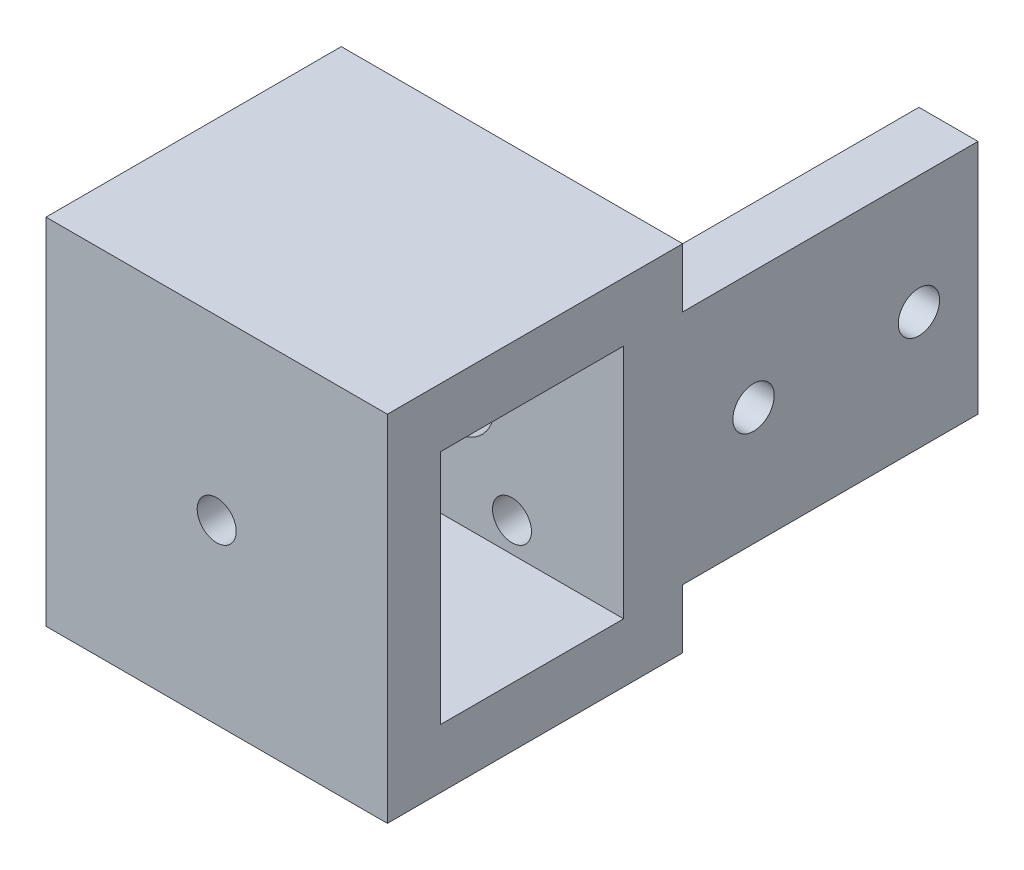
SolidWorks part; units mm, degrees
ref_plane "前视基准面" through (0, 0, 0) normal (0, 0, 1) x (1, 0, 0)
ref_plane "上视基准面" through (0, 0, 0) normal (0, 1, 0) x (1, 0, 0)
ref_plane "右视基准面" through (0, 0, 0) normal (1, 0, 0) x (0, 0, -1)
sketch "草图1" plane through (0, 0, 0) normal (0, 0, 1) x (1, 0, 0)
  line L0 (0, 10) -> (28.9, 10) construction
  line L1 (0, 20) -> (28.9, 20)
  line L2 (0, 20) -> (0, 0)
  line L3 (0, 0) -> (28.9, 0)
  line L4 (28.9, 20) -> (28.9, 0)
  line L6 (14.45, 20) -> (14.45, -18.7145) construction
  line L11 (0, 20) -> (28.9, 20)
  line L12 (0, 20) -> (0, 25)
  line L13 (0, 25) -> (28.9, 25)
  line L14 (28.9, 20) -> (28.9, 25)
  line L15 (0, 0) -> (28.9, 0)
  line L16 (0, 0) -> (0, -5)
  line L17 (0, -5) -> (28.9, -5)
  line L18 (28.9, 0) -> (28.9, -5)
  circle A0 centre (9.45, 17.5) radius 1.65
  circle A1 centre (19.45, 17.5) radius 1.65
  circle A2 centre (9.45, 2.5) radius 1.65
  circle A3 centre (19.45, 2.5) radius 1.65
  dimension "D3" = 3.3
  dimension "D5" = 2.5
  dimension "D1" = 20
  dimension "D2" = 28.9
  dimension "D4" = 9.45
  dimension "D6" = 5
  dimension "D7" = 5
extrude "凸台-拉伸1" add sketch "草图1" along normal blind 5 contours L4 L1 L2 L3 A3 A1 A0 A2 | L4 region at (14.45, 10, 0)
sketch "草图2" plane through (28.9, 0, 0) normal (1, 0, 0) x (0, 0, -1)
  line L1 (0, 0) -> (25, 0)
  line L2 (0, 0) -> (0, 20)
  line L3 (0, 20) -> (25, 20)
  line L4 (25, 0) -> (25, 20)
  line L5 (0, 10) -> (-8.8153, 10) construction
  line L6 (-5, 20) -> (0, 20) construction
  circle A0 centre (20, 10) radius 1.75
  circle A1 centre (6, 10) radius 1.75
  point P8 (0, 10)
  dimension "D2" = 3.5
  dimension "D3" = 3.5
  dimension "D4" = 14
  dimension "D5" = 5
  dimension "D1" = 25
extrude "凸台-拉伸4" add sketch "草图1<5>" along normal blind 25 contours L18 L3 L16 L17 | L1 L14 L13 L12 region at (14.45, 22.5, 0) region at (14.45, -2.5, 0)
sketch "草图1<5>" plane through (0, 0, 0) normal (0, 0, 1) x (1, 0, 0) same geometry as "草图1"
extrude "凸台-拉伸5" add sketch "草图2" against normal blind 5
sketch "草图3" plane through (0, 0, 25) normal (0, 0, 1) x (1, 0, 0)
  line L0 (0, 10) -> (28.9, 10) construction
  line L1 (0, 20) -> (28.9, 20)
  line L2 (0, 20) -> (0, 0)
  line L3 (0, 0) -> (28.9, 0)
  line L4 (28.9, 20) -> (28.9, 0)
  line L5 (14.45, 20) -> (14.45, 0) construction
  circle A0 centre (14.45, 10) radius 1.65
  dimension "D1" = 3.3
extrude "凸台-拉伸6" add sketch "草图3" against normal blind 4.5
sketch "草图4" plane through (0, 0, 20.5) normal (0, 0, -1) x (-1, 0, 0)
  circle A0 centre (-14.45, 10) radius 3.5
  dimension "D1" = 7
extrude "切除-拉伸1" cut sketch "草图4" along normal up to next
